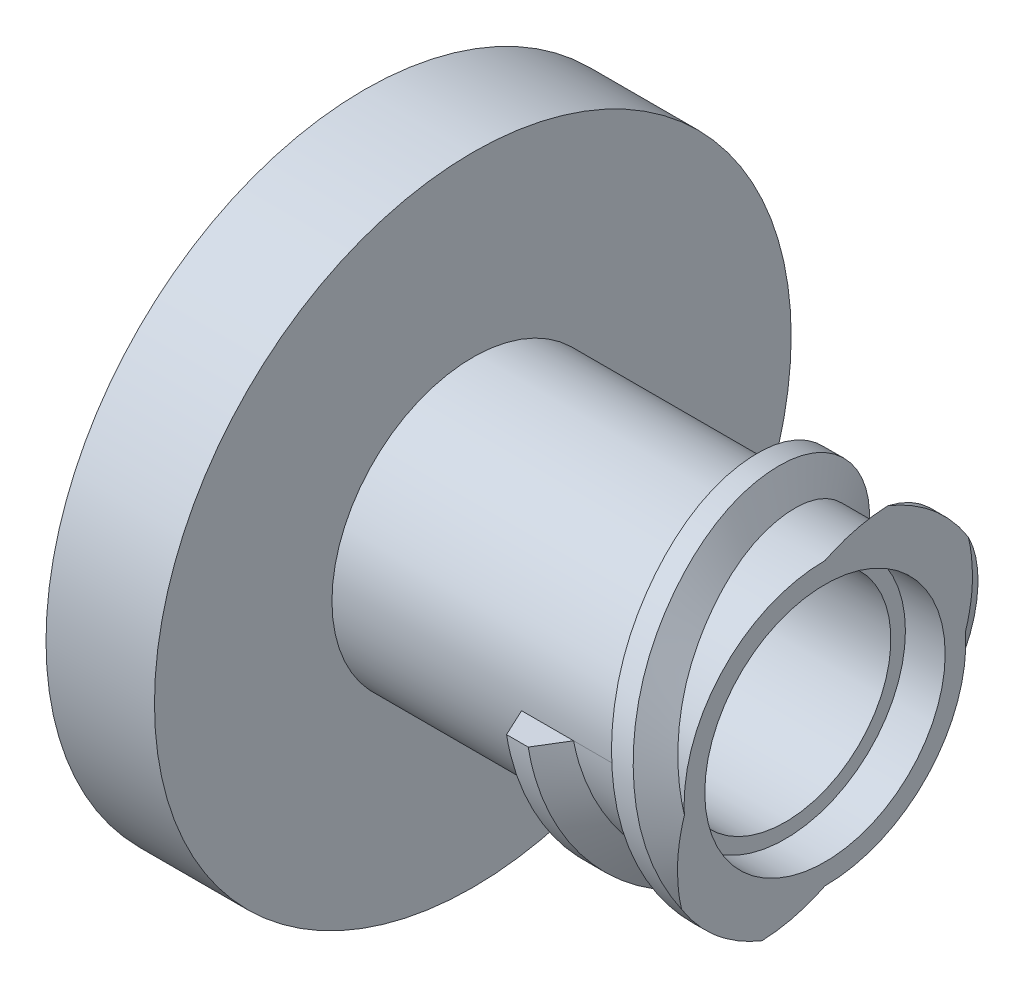
SolidWorks part; units mm, degrees
ref_plane "Front Plane" through (0, 0, 0) normal (0, 0, 1) x (1, 0, 0)
ref_plane "Top Plane" through (0, 0, 0) normal (0, 1, 0) x (1, 0, 0)
ref_plane "Right Plane" through (0, 0, 0) normal (1, 0, 0) x (0, 0, -1)
sketch "Sketch1" plane through (0, 0, 0) normal (0, 0, 1) x (1, 0, 0)
  line L7 (7, 0.75) -> (7, 2.26)
  line L8 (0, 0) -> (16, 0) construction
  line L9 (7, 2.26) -> (7.77, 2.26)
  line L10 (7.77, 2.26) -> (7.77, 1)
  line L11 (7.77, 1) -> (10.27, 1)
  line L12 (10.27, 1) -> (10.27, 0.8534)
  line L13 (10.27, 0.8534) -> (9.9877, 0.8534)
  line L14 (9.9877, 0.8534) -> (9.9877, 0.75)
  line L15 (9.9877, 0.75) -> (7, 0.75)
  dimension "D1" = 0.75
  dimension "D2" = 1
  dimension "D3" = 2.5
  dimension "D4" = 0.77
  dimension "D5" = 3.27
  dimension "D6" = 2.26
revolve "Revolve1" add sketch "Sketch1" angle 360 about L8
sketch "Sketch2" plane through (10.27, 0, 0) normal (1, 0, 0) x (0, 0, -1)
  circle A0 centre (0, 0) radius 1
  circle A1 centre (0, 0) radius 1 construction
curve "Helix/Spiral1" pitch 1.5385 height 1.5385 radius 1 centre (10.27, 0, 0) axis (-1, 0, 0) start towards (0, 0, 1)
sketch "Sketch4" plane through (0, 0, 0) normal (0, 0, 1) x (1, 0, 0)
  line L0 (10.27, 1) -> (10.6392, 1)
  line L1 (10.27, 1) -> (7.77, 1) construction
  line L2 (10.6392, 1) -> (10.5171, 1.2)
  line L3 (10.5171, 1.2) -> (10.3633, 1.2)
  line L4 (10.3633, 1.2) -> (10.27, 1)
  line L5 (10.27, 1) -> (7.77, 1) construction
  line L6 (10.27, 1) -> (10.27, 4.1152) construction
  line L7 (10.27, -1) -> (10.27, 1) construction
  point P4 (13.9996, 1)
  point P9 (12, 1)
  dimension "D1" = 0.1538
  dimension "D2" = 0.3692
  dimension "D3" = 0.2
  dimension "D4" = 25
sweep "Sweep2" add profiles "Sketch4" path "Helix/Spiral1"
pattern_circular "CirPattern2" count 2 over 360 about axis through (10.27, 0, 0) along (-1, 0, 0) of "Sweep2"
sketch "Sketch6" plane through (10.27, 0, 0) normal (1, 0, 0) x (0, 0, -1)
  circle A0 centre (0, 0) radius 4.6219
extrude "Cut-Extrude1" cut sketch "Sketch6" along normal blind 10
ref_plane "Plane1" through (14.5, 0, 0) normal (1, 0, 0) x (0, 0, -1)
